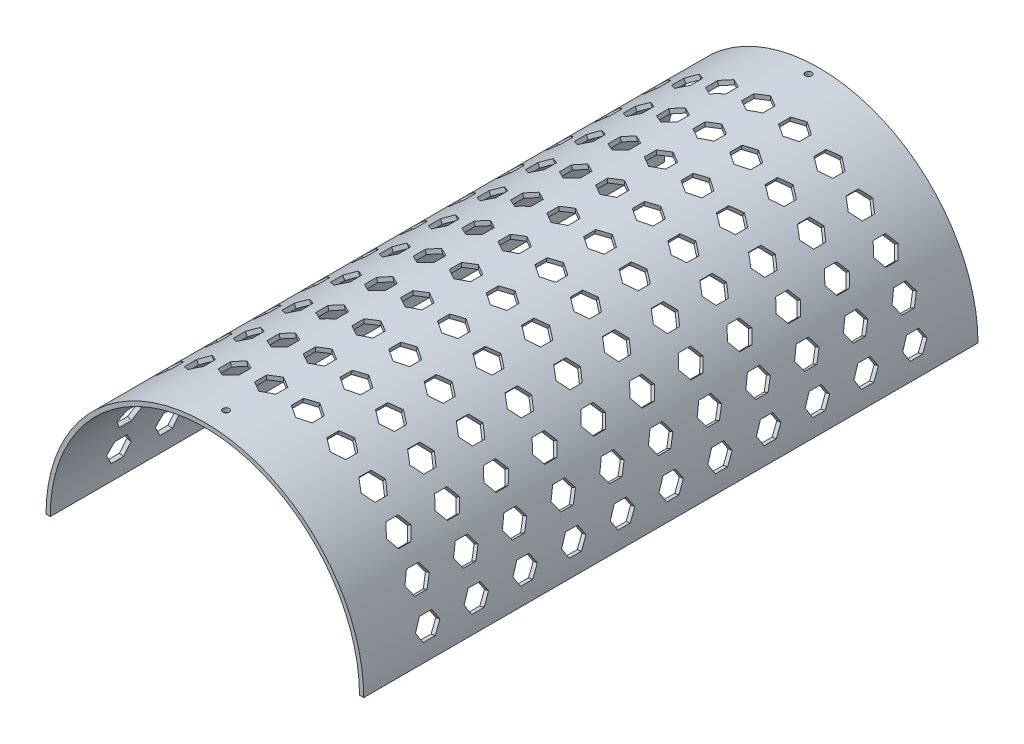
SolidWorks part; units mm, degrees
material "PET"
ref_plane "Front Plane" through (0, 0, 0) normal (0, 0, 1) x (1, 0, 0)
ref_plane "Top Plane" through (0, 0, 0) normal (0, 1, 0) x (1, 0, 0)
ref_plane "Right Plane" through (0, 0, 0) normal (1, 0, 0) x (0, 0, -1)
sketch "Sketch1" plane through (0, 0, 0) normal (0, 0, 1) x (1, 0, 0)
  line L0 (-75, 0) -> (-73, 0)
  line L1 (-73, 0) -> (73, 0) construction
  line L2 (73, 0) -> (75, 0)
  arc A0 (75, 0) -> (-75, 0) centre (0, 0) ccw
  arc A1 (73, 0) -> (-73, 0) centre (0, 0) ccw
  arc A2 (-75, 0) -> (75, 0) centre (0, 0) ccw construction
  circle A3 centre (0, 0) radius 75 construction
  arc A4 (-73, 0) -> (73, 0) centre (0, 0) ccw construction
  circle A5 centre (0, 0) radius 73 construction
  dimension "D1" = 150
  dimension "D2" = 2
extrude "Boss-Extrude1" add sketch "Sketch1" along normal blind 290
sketch "Sketch4" plane through (0, 0, 0) normal (0, 1, 0) x (1, 0, 0)
  line L0 (-75, -290) -> (75, -290) construction
  line L1 (75, 0) -> (-75, 0) construction
  circle A0 centre (0, -5) radius 1.5
  circle A1 centre (0, -280) radius 1.5
  dimension "D1" = 3
  dimension "D3" = 3
  dimension "D2" = 10
  dimension "D4" = 5
extrude "Cut-Extrude2" cut sketch "Sketch4" along normal up to surface (75 mm away) up to face at (0, 37.5, 145)
sketch "Sketch2" plane through (0, 0, 0) normal (0, 1, 0) x (1, 0, 0)
  line L0 (0, 0) -> (0, -28.6927) construction
  line L1 (5, -31.5794) -> (5, -25.8059)
  line L2 (5, -25.8059) -> (0, -22.9192)
  line L3 (0, -22.9192) -> (-5, -25.8059)
  line L4 (-5, -25.8059) -> (-5, -31.5794)
  line L5 (-5, -31.5794) -> (0, -34.4662)
  line L6 (0, -34.4662) -> (5, -31.5794)
  circle A1 centre (0, -28.6927) radius 5 construction
  dimension "D1" = 10
extrude "Cut-Extrude3" cut sketch "Sketch2" along normal up to surface (74.8331 mm away) up to face at (0, 37.5, 145)
pattern_circular "CirPattern1" count 7 every 13.333 about axis through (0, 0, 290) along (0, 0, -1) of "Cut-Extrude3" reverse direction yes other way count 7
pattern_linear "LPattern1" count 11 spacing 23 along (0, 0, 1) of "CirPattern1", "Cut-Extrude3"
